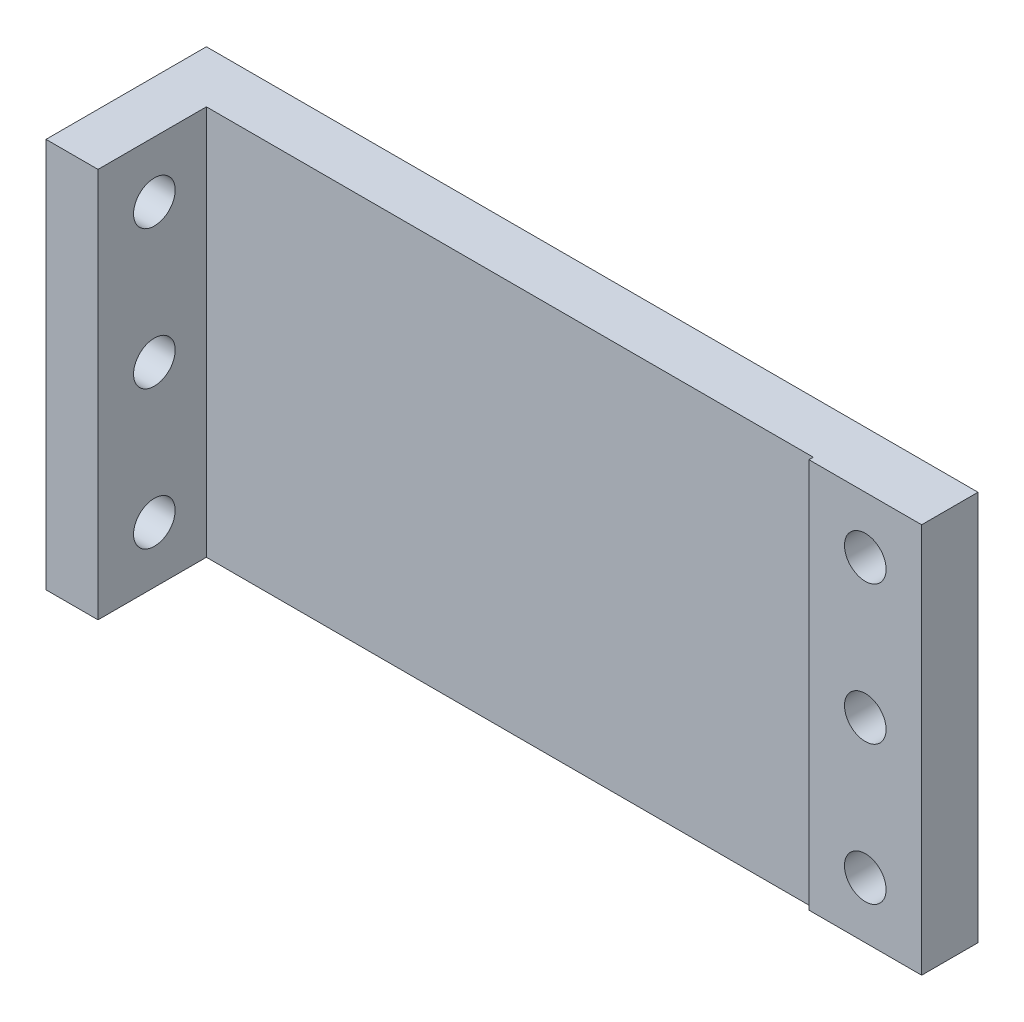
SolidWorks part; units mm, degrees
ref_plane "Plano frontal" through (0, 0, 0) normal (0, 0, 1) x (1, 0, 0)
ref_plane "Plano superior" through (0, 0, 0) normal (0, 1, 0) x (1, 0, 0)
ref_plane "Plano direito" through (0, 0, 0) normal (1, 0, 0) x (0, 0, -1)
sketch "Esboço1" plane through (0, 0, 0) normal (0, 0, 1) x (1, 0, 0)
  line L0 (-16, 3.25) -> (-16, -3.25) construction
  line L1 (-16.25, -11.25) -> (25.25, -11.25)
  line L2 (-16.25, -11.25) -> (-16.25, 11.25)
  line L3 (-16.25, 11.25) -> (25.25, 11.25)
  line L4 (25.25, -11.25) -> (25.25, 11.25)
  line L6 (22, -8) -> (22, -11.25) construction
  line L7 (22, -8) -> (25.25, -8) construction
  line L9 (22, 8) -> (22, 11.25) construction
  line L11 (25.5, -8.2779) -> (25.5, 29.7721) construction
  dimension "D1" = 0.25
  dimension "D2" = 0.25
extrude "Ressalto-extrusão1" add sketch "Esboço1" against normal blind 3
sketch "Esboço2" plane through (-16.25, 0, 0) normal (-1, 0, 0) x (0, 0, 1)
  line L1 (-3, -11.25) -> (6.25, -11.25)
  line L2 (-3, -11.25) -> (-3, 11.25)
  line L3 (-3, 11.25) -> (6.25, 11.25)
  line L4 (6.25, -11.25) -> (6.25, 11.25)
  line L5 (6.5, 29.8) -> (6.5, 13.8) construction
  line L6 (-3, 11.25) -> (0, 11.25) construction
  dimension "D1" = 0.25
extrude "Ressalto-extrusão2" add sketch "Esboço2" along normal blind 3
sketch "Esboço3" plane through (0, 0, -3) normal (0, 0, 1) x (1, 0, 0)
  line L0 (25.25, 11.25) -> (-16.25, 11.25) construction
  line L1 (25.25, -11.25) -> (18.75, -11.25)
  line L2 (25.25, -11.25) -> (25.25, 11.25)
  line L3 (25.25, 11.25) -> (18.75, 11.25)
  line L4 (18.75, -11.25) -> (18.75, 11.25)
  line L5 (18.75, 16) -> (25.25, 16) construction
  circle A0 centre (22, 16) radius 1.25 construction
  point P9 (22, 16)
extrude "Ressalto-extrusão3" add sketch "Esboço3" along normal offset from surface (3.25 mm away) 0.25
hole_wizard "Rebaixo para parafuso com cabeça redonda de M21" positions "Esboço4" profile "Esboço5" counterbore size "M2" standard "DIN" end condition through all
sketch "Esboço4" plane through (-19.25, 0, 0) normal (-1, 0, 0) x (0, 0, 1)
  circle A0 centre (3, 8) radius 1.25 construction
  circle A1 centre (3, -8) radius 1.25 construction
  circle A2 centre (3, 0) radius 1.25 construction
  point P0 (3, 8)
  point P7 (3, -8)
  point P13 (3, 0)
sketch "Esboço5" plane through (-19.25, 8, 3) normal (0, 1, 0) x (0, 0, 1)
  line L0 (0, 0) -> (0, 44.5)
  line L1 (0, 44.5) -> (1.2, 44.5)
  line L3 (1.2, 44.5) -> (1.2, 0.7)
  line L4 (1.2, 0.7) -> (2.2, 0.7)
  line L5 (2.2, 0.7) -> (2.2, 0)
  line L7 (2.2, 0) -> (0, 0)
  line L11 (0, -6.35) -> (0, 107.95) construction
  dimension "Thru Hole Dia." = 2.4
  dimension "Thru Hole Depth" = 44.5
  dimension "C'Bore Dia." = 4.4
  dimension "C'Bore Depth" = 0.7
hole_wizard "Rebaixo para parafuso com cabeça redonda de M22" positions "Esboço6" profile "Esboço7" counterbore size "M2" standard "DIN" end condition through all
sketch "Esboço6" plane through (0, 0, -3) normal (0, 0, -1) x (-1, 0, 0)
  circle A0 centre (-22, 8) radius 1.25 construction
  point P0 (-22, 8)
  point P6 (-22, 0)
  point P9 (-22, -8)
sketch "Esboço7" plane through (22, 8, -3) normal (1, 0, 0) x (0, 1, 0)
  line L0 (0, 0) -> (0, 9.25)
  line L1 (0, 9.25) -> (1.2, 9.25)
  line L3 (1.2, 9.25) -> (1.2, 0.7)
  line L4 (1.2, 0.7) -> (2.2, 0.7)
  line L5 (2.2, 0.7) -> (2.2, 0)
  line L7 (2.2, 0) -> (0, 0)
  line L11 (0, -6.35) -> (0, 107.95) construction
  dimension "Thru Hole Dia." = 2.4
  dimension "Thru Hole Depth" = 9.25
  dimension "C'Bore Dia." = 4.4
  dimension "C'Bore Depth" = 0.7
move or copy body "Corpo-Mover/Copiar1" [suppressed] bodies to move or copy 102 103
